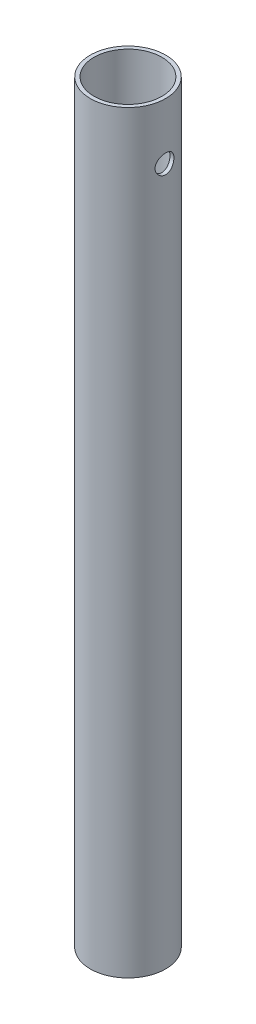
SolidWorks part; units mm, degrees
ref_plane "Ön Düzlem" through (0, 0, 0) normal (0, 0, 1) x (1, 0, 0)
ref_plane "Üst Düzlem" through (0, 0, 0) normal (0, 1, 0) x (1, 0, 0)
ref_plane "Sağ Düzlem" through (0, 0, 0) normal (1, 0, 0) x (0, 0, -1)
sketch "Çizim1" plane through (0, 0, 0) normal (0, 1, 0) x (1, 0, 0)
  circle A0 centre (0, 0) radius 10
  circle A1 centre (0, 0) radius 9
  dimension "D1" = 20
  dimension "D2" = 18
extrude "Yükseklik-Ekstrüzyon1" add sketch "Çizim1" along normal blind 200
sketch "Çizim2" plane through (0, 0, 0) normal (1, 0, 0) x (0, 0, -1)
  line L0 (10, 200) -> (-10, 200) construction
  circle A0 centre (0, 185) radius 2.5
  dimension "D2" = 5
  dimension "D1" = 15
extrude "Kes-Ekstrüzyon1" cut sketch "Çizim2" against normal blind 20 and the other way blind 20
